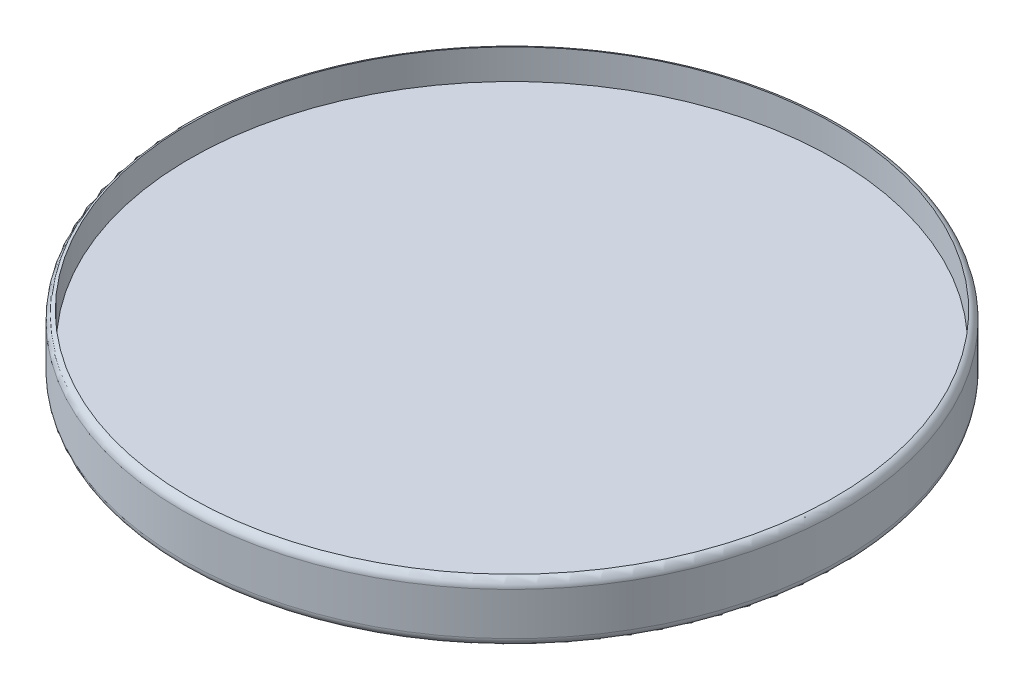
SolidWorks part; units mm, degrees
ref_plane "Front Plane" through (0, 0, 0) normal (0, 0, 1) x (1, 0, 0)
ref_plane "Top Plane" through (0, 0, 0) normal (0, 1, 0) x (1, 0, 0)
ref_plane "Right Plane" through (0, 0, 0) normal (1, 0, 0) x (0, 0, -1)
sketch "Sketch1" plane through (0, 0, 0) normal (0, 1, 0) x (1, 0, 0)
  line L0 (-2.1753, 1.4397) -> (-1.0811, -2.374)
  line L1 (-1.0811, -2.374) -> (2.1753, -1.4397)
  line L2 (2.1753, -1.4397) -> (1.0811, 2.374)
  line L3 (1.0811, 2.374) -> (-2.1753, 1.4397)
  circle A0 centre (0, 0) radius 47.498
  circle A1 centre (0, 0) radius 2.6086
  circle A2 centre (0, 0) radius 46.5455
  dimension "D1" = 93.091
  dimension "D2" = 5.2172
  dimension "D3" = 94.996
extrude "Boss-Extrude1" add sketch "Sketch1" along normal blind 3.1242 contours A2 A1 | L2 A1 | L0 A1 region at (-1.9858, 0, 0.5698) region at (1.9858, 0, -0.5698) region at (-45.229, 0, 0)
extrude "Boss-Extrude2" add sketch "Sketch1<5>" along normal blind 8.636 contours A0 A2 region at (-47.3637, 0, 0)
sketch "Sketch1<5>" plane through (0, 0, 0) normal (0, 1, 0) x (1, 0, 0) same geometry as "Sketch1"
sketch "Sketch2" plane through (0, 3.1242, 0) normal (0, 1, 0) x (1, 0, 0)
  circle A0 centre (0, 0) radius 46.4312
  circle A1 centre (-46.2373, -4.2392) radius 5.0742
  arc M1 (2.1753, -1.4397) -> (-1.0811, -2.374) centre (0, 0) cw
  line M2 (-1.0811, -2.374) -> (-2.1753, 1.4397)
  arc M3 (-2.1753, 1.4397) -> (1.0811, 2.374) centre (0, 0) cw
  line M4 (1.0811, 2.374) -> (2.1753, -1.4397)
fillet "Fillet1" radius 1.27 1 edges at (0, 0, 47.498)
fillet "Fillet2" radius 1.27 1 edges at (0, 8.636, 47.498)
extrude "Boss-Extrude3" add sketch "Sketch2" along normal blind 0.508 contours A1 A0 M4 M1 M2 M3 | A0 A1 region at (4.5215, 3.1242, 44.8909) region at (-44.0438, 3.1242, 4.0381)
sketch "Sketch3" plane through (0, 3.6322, 0) normal (0, 1, 0) x (1, 0, 0)
  circle A0 centre (0, 0) radius 46.4312
extrude "Boss-Extrude4" add sketch "Sketch3" along normal blind 0.762
